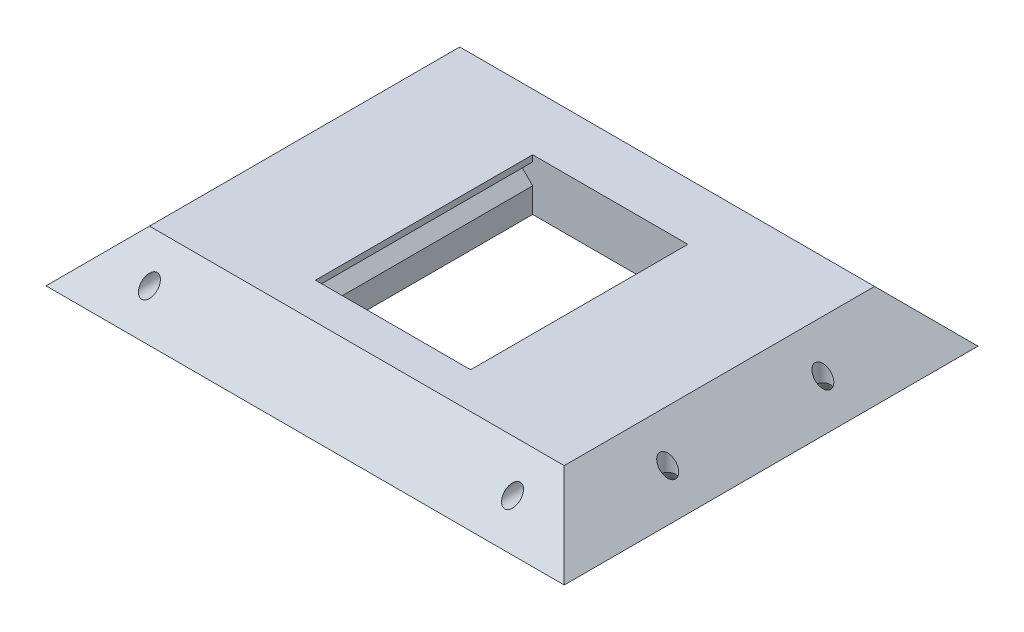
SolidWorks part; units mm, degrees
ref_plane "Спереди" through (0, 0, 0) normal (0, 0, 1) x (1, 0, 0)
ref_plane "Сверху" through (0, 0, 0) normal (0, 1, 0) x (1, 0, 0)
ref_plane "Справа" through (0, 0, 0) normal (1, 0, 0) x (0, 0, -1)
sketch "Эскиз1" plane through (0, 0, 0) normal (0, 1, 0) x (1, 0, 0)
  line L1 (-50.1, -40) -> (50.1, -40)
  line L2 (-50.1, -40) -> (-50.1, 40)
  line L3 (-50.1, 40) -> (50.1, 40)
  line L4 (50.1, -40) -> (50.1, 40)
  line L5 (-50.1, -40) -> (50.1, 40) construction
  line L6 (-50.1, 40) -> (50.1, -40) construction
  point P0 (0, 0)
  dimension "D1" = 100.2
  dimension "D2" = 80
ref_plane "Плоскость1" through (0, 10, 0) normal (0, 1, 0) x (1, 0, 0)
sketch "Эскиз2" plane through (0, 10, 0) normal (0, 1, 0) x (1, 0, 0)
  line L4 (50.1, -40) -> (50.1, 40) construction
  line L5 (-50.1, -40) -> (50.1, -40) construction
  line L6 (-50.1, -40) -> (-50.1, 40) construction
  line L7 (-50.1, 40) -> (50.1, 40) construction
  line L8 (40.1, -30) -> (40.1, 30)
  line L9 (-40.1, -30) -> (40.1, -30)
  line L10 (-40.1, 30) -> (-40.1, -30)
  line L11 (40.1, 30) -> (-40.1, 30)
  line L12 (40.1, -30) -> (40.1, 30)
  line L13 (-40.1, -30) -> (40.1, -30)
  line L14 (-40.1, 30) -> (-40.1, -30)
  line L15 (40.1, 30) -> (-40.1, 30)
  line L16 (50.1, -40) -> (50.1, 40) construction
  line L17 (-50.1, -40) -> (50.1, -40) construction
  line L18 (-50.1, -40) -> (-50.1, 40) construction
  line L19 (-50.1, 40) -> (50.1, 40) construction
  line L20 (-40.1, -30) -> (-50.1, -30) construction
  line L21 (-40.1, -30) -> (-40.1, -40) construction
  line L22 (40.1, -30) -> (40.1, -40) construction
  line L23 (40.1, -30) -> (50.1, -30) construction
  line L24 (40.1, 30) -> (50.1, 30) construction
  line L25 (40.1, 30) -> (40.1, 40) construction
  line L26 (-40.1, 30) -> (-50.1, 30) construction
  line L27 (-40.1, 30) -> (-40.1, 40) construction
  dimension "D1" = 10
loft "По сечениям1" add profiles "Эскиз1", "Эскиз2" connector at (-50.1, 0, -40) connector at (-40.1, 10, -30)
ref_plane "Плоскость2" through (0, 0, 40) normal (0, 0, 1) x (1, 0, 0)
sketch "Эскиз4" plane through (0, 0, 40) normal (0, 0, 1) x (1, 0, 0)
  line L0 (-50.1, 10) -> (-50.1, 0) construction
  line L1 (50.1, 0) -> (50.1, 10) construction
  line L2 (-50.1, 10) -> (50.1, 10) construction
  line L3 (-50.1, 10) -> (50.1, 10) construction
  line L4 (-40.1, 10) -> (-40.1, 0) construction
  line L5 (-50.1, 0) -> (50.1, 0) construction
  line L6 (-30.1, 10) -> (-30.1, 0) construction
  line L7 (-40.1, 5) -> (-30.1, 5) construction
  line L8 (0, 0) -> (0, 10) construction
  circle A0 centre (-35.1, 5) radius 1.5
  circle A1 centre (35.1, 5) radius 1.5
  dimension "D2" = 3
  dimension "D1" = 10
extrude "Вырез-Вытянуть1" cut sketch "Эскиз4" against normal blind 20
mirror "Зеркальное отражение1" about plane through (0, 0, 0) normal (0, 0, 1) of "Вырез-Вытянуть1"
sketch "Эскиз5" plane through (0, 0, 0) normal (0, -1, 0) x (1, 0, 0)
  line L0 (40.1, 30) -> (40.1, -30) construction
  line L1 (-40.1, 30) -> (40.1, 30) construction
  line L2 (40.1, -30) -> (-40.1, -30) construction
  line L3 (-40.1, -30) -> (-40.1, 30) construction
  line L4 (40.1, 30) -> (40.1, -30) construction
  line L5 (-40.1, 30) -> (40.1, 30) construction
  line L6 (40.1, -30) -> (-40.1, -30) construction
  line L7 (-40.1, -30) -> (-40.1, 30) construction
  line L8 (-40.1, 20) -> (-50.1, 20) construction
  line L10 (-50.1, 40) -> (-50.1, -40) construction
  line L11 (-40.1, 10) -> (-50.1, 10) construction
  line L12 (0, -40) -> (0, 40) construction
  line L13 (-50.1, -40) -> (50.1, -40) construction
  line L14 (-50.1, 40) -> (50.1, 40) construction
  line L15 (-50.1, 0) -> (50.1, 0) construction
  line L16 (50.1, 40) -> (50.1, -40) construction
  line L17 (-45.1, 20) -> (-45.1, 10) construction
  circle A0 centre (-45.1, 15) radius 1.5
  circle A1 centre (-45.1, -15) radius 1.5
  circle A2 centre (45.1, -15) radius 1.5
  circle A3 centre (45.1, 15) radius 1.5
  dimension "D3" = 3
  dimension "D1" = 10
  dimension "D2" = 20
extrude "Вырез-Вытянуть2" cut sketch "Эскиз5" against normal through all contours A2 | A3 | A1 | A0
sketch "Sketch1" plane through (0, 0, 0) normal (0, -1, 0) x (1, 0, 0)
  line L0 (-50.1, 0) -> (50.1, 0) construction
  line L1 (-50.1, -40) -> (-50.1, 40) construction
  line L2 (50.1, 40) -> (50.1, -40) construction
  line L3 (0, 40) -> (0, -40) construction
  line L4 (-50.1, 40) -> (50.1, 40) construction
  line L5 (50.1, -40) -> (-50.1, -40) construction
  circle A0 centre (-45.1, 15) radius 3.3
  dimension "D1" = 6.6
ref_plane "Plane1" through (0, 2.8, 0) normal (0, -1, 0) x (-1, 0, 0)
sketch "Sketch2" plane through (0, 2.8, 0) normal (0, -1, 0) x (-1, 0, 0)
  line L0 (50.1, 0) -> (-50.1, 0) construction
  line L1 (50.1, 0) -> (-50.1, 0) construction
  line L2 (0, -40) -> (0, 40) construction
  line L3 (0, -40) -> (0, 40) construction
  circle A0 centre (45.1, -15) radius 1.5 construction
  circle A1 centre (45.1, -15) radius 1.5
ref_plane "Plane2" through (0, 0, 0) normal (0, 0, 1) x (1, 0, 0)
loft "Cut-Loft1" cut profiles "Sketch2", "Sketch1" connector at (-43.9235, 2.8, 15.9305) connector at (-43.8813, 0, 18.0667)
mirror "Mirror1" about plane through (0, 0, 0) normal (0, 0, 1) of "Cut-Loft1"
ref_plane "Plane3" through (0, 0, 0) normal (1, 0, 0) x (0, 0, -1)
mirror "Mirror2" about plane through (0, 0, 0) normal (1, 0, 0) of "Mirror1", "Cut-Loft1"
sketch "Sketch3" plane through (0, 0, 0) normal (0, -1, 0) x (1, 0, 0)
  line L0 (0, 40) -> (0, -40) construction
  line L1 (-50.1, 40) -> (50.1, 40) construction
  line L2 (50.1, -40) -> (-50.1, -40) construction
  line L4 (-15, 23) -> (15, 23)
  line L5 (-15, 23) -> (-15, -19)
  line L6 (-15, -19) -> (15, -19)
  line L7 (15, 23) -> (15, -19)
  line L8 (-15, 23) -> (15, -19) construction
  line L9 (-15, -19) -> (15, 23) construction
  point P10 (0, 2)
  point P11 (0, 0)
  dimension "D1" = 30
  dimension "D2" = 42
  dimension "D3" = 21
extrude "Cut-Extrude1" cut sketch "Sketch3" against normal through all
sketch "Sketch4" plane through (0, 0, -19) normal (0, 0, 1) x (1, 0, 0)
  line L0 (0, 0) -> (0, 10) construction
  line L1 (-15, 0) -> (15, 0) construction
  line L2 (15, 10) -> (-15, 10) construction
  line L3 (-15, 8.8) -> (-17, 6.8)
  line L4 (-15, 10) -> (-15, 0) construction
  line L5 (-17, 6.8) -> (-15, 4.8)
  line L6 (-15, 4.8) -> (-15, 8.8)
  line L7 (15, 4.8) -> (15, 8.8)
  line L8 (17, 6.8) -> (15, 4.8)
  line L9 (15, 8.8) -> (17, 6.8)
  dimension "D1" = 1.2
  dimension "D2" = 2
  dimension "D3" = 45
extrude "Cut-Extrude2" cut sketch "Sketch4" along normal up to surface (42 mm away) up to face at (0, 5, 23)
